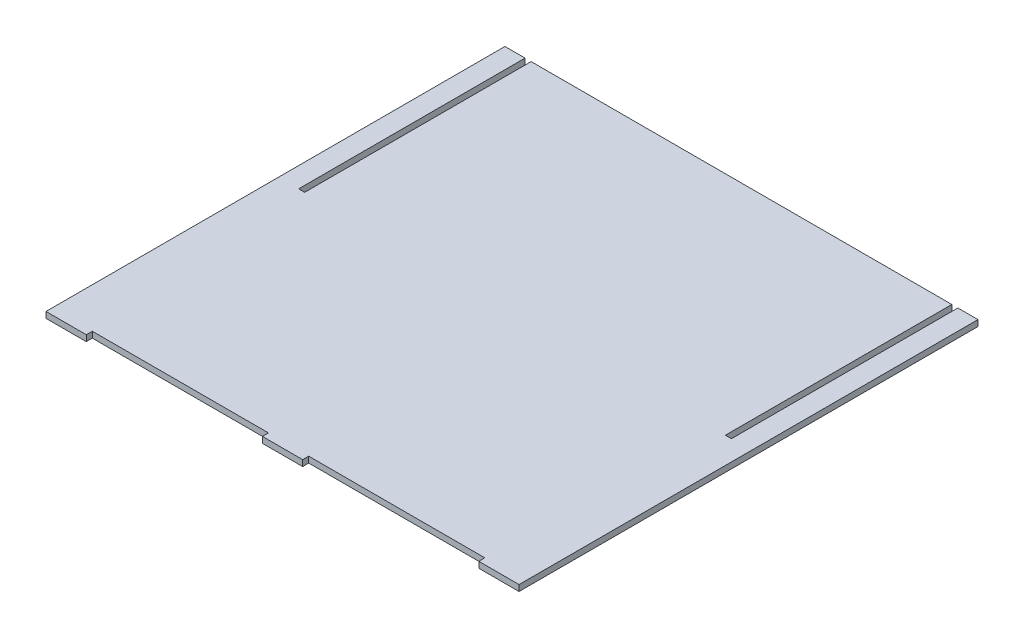
SolidWorks part; units mm, degrees
ref_plane "Front Plane" through (0, 0, 0) normal (0, 0, 1) x (1, 0, 0)
ref_plane "Top Plane" through (0, 0, 0) normal (0, 1, 0) x (1, 0, 0)
ref_plane "Right Plane" through (0, 0, 0) normal (1, 0, 0) x (0, 0, -1)
sketch "Sketch1" plane through (0, 0, 0) normal (0, 1, 0) x (1, 0, 0)
  line L0 (-470, 0) -> (-430, 0)
  line L2 (0, 0) -> (0, 456)
  line L3 (0, 456) -> (-470, 456)
  line L4 (-470, 0) -> (-470, 456)
  line L5 (-430, 0) -> (-430, 6)
  line L6 (0, 0) -> (-40, 0)
  line L7 (-40, 0) -> (-40, 6)
  line L8 (-40, 6) -> (-215, 6)
  line L9 (-215, 6) -> (-215, 0)
  line L10 (-215, 0) -> (-255, 0)
  line L11 (-255, 0) -> (-255, 6)
  line L12 (-255, 6) -> (-430, 6)
  dimension "D1" = 470
  dimension "D2" = 456
  dimension "D3" = 40
  dimension "D4" = 6
extrude "Boss-Extrude1" add sketch "Sketch1" along normal blind 6 contours L4 L3 L2 L6 L7 L8 L9 L10 L11 L12 L5 L0
sketch "Sketch2" plane through (0, 6, 0) normal (0, 1, 0) x (1, 0, 0)
  line L1 (-20, 456) -> (-26, 456)
  line L2 (-20, 456) -> (-20, 231)
  line L3 (-20, 231) -> (-26, 231)
  line L4 (-26, 456) -> (-26, 231)
  line L6 (0, 0) -> (0, 456) construction
  line L7 (0, 456) -> (-470, 456) construction
  dimension "D1" = 6
  dimension "D2" = 20
  dimension "D3" = 225
extrude "Cut-Extrude1" cut sketch "Sketch2" against normal blind 6
pattern_linear "LPattern1" count 2 spacing 424 along (-1, 0, 0) of "Cut-Extrude1"
